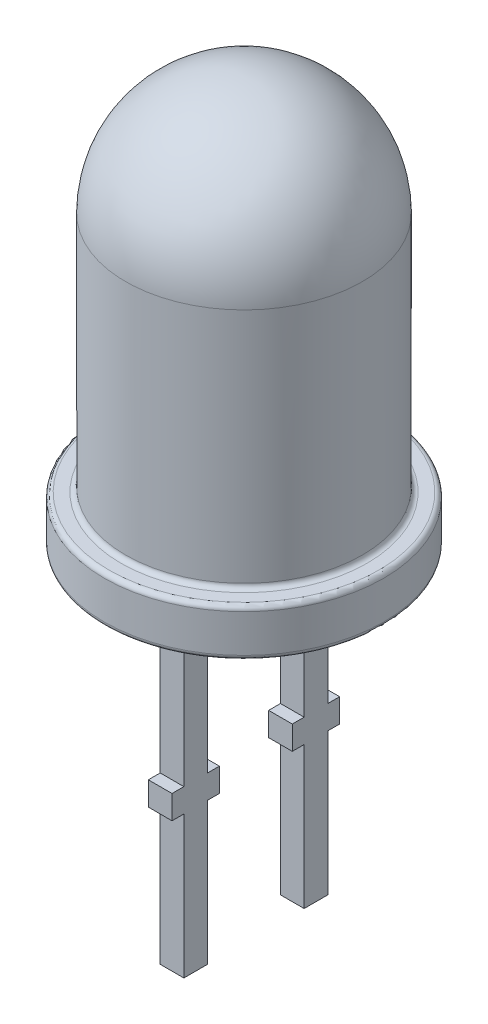
SolidWorks part; units mm, degrees
ref_plane "Спереди" through (0, 0, 0) normal (0, 0, 1) x (1, 0, 0)
ref_plane "Сверху" through (0, 0, 0) normal (0, 1, 0) x (1, 0, 0)
ref_plane "Справа" through (0, 0, 0) normal (1, 0, 0) x (0, 0, -1)
sketch "Эскиз1" plane through (0, 0, 0) normal (1, 0, 0) x (0, 0, -1)
  line L0 (4.8309, 0) -> (-4.1566, 0) construction
  line L1 (4.8309, 4) -> (-4.1566, 4) construction
  line L2 (0, -8.9757) -> (0, 8.1567) construction
  line L3 (-1.27, 7.7097) -> (-1.27, -11.3357) construction
  line L4 (-1.52, 4) -> (-1.52, 0.5)
  line L5 (-1.52, 0.5) -> (-1.77, 0.5)
  line L6 (-1.77, 0.5) -> (-1.77, 0)
  line L7 (-1.77, 0) -> (-1.52, 0)
  line L8 (-1.52, 0) -> (-1.52, -3)
  line L9 (-1.52, -3) -> (-1.02, -3)
  line L10 (-1.02, 0.5) -> (-1.02, 0) construction
  line L11 (-1.52, 0.5) -> (-1.52, 0) construction
  line L12 (-1.02, 0) -> (-1.02, -3)
  line L13 (-0.77, 0) -> (-1.02, 0)
  line L14 (-0.77, 0.5) -> (-0.77, 0)
  line L15 (-1.02, 0.5) -> (-0.77, 0.5)
  line L16 (-1.02, 4) -> (-1.02, 0.5)
  line L17 (1.52, 0.5) -> (1.52, 0) construction
  line L18 (1.02, 0.5) -> (1.02, 0) construction
  line L19 (1.02, 4) -> (1.02, 0.5)
  line L20 (1.02, 0.5) -> (0.77, 0.5)
  line L21 (0.77, 0.5) -> (0.77, 0)
  line L22 (0.77, 0) -> (1.02, 0)
  line L23 (1.02, 0) -> (1.02, -3)
  line L24 (1.52, -3) -> (1.02, -3)
  line L25 (1.52, 0) -> (1.52, -3)
  line L26 (1.77, 0) -> (1.52, 0)
  line L27 (1.77, 0.5) -> (1.77, 0)
  line L28 (1.52, 0.5) -> (1.77, 0.5)
  line L29 (1.52, 4) -> (1.52, 0.5)
  line L30 (-3.3588, 8) -> (3.258, 8) construction
  line L31 (1.52, 4) -> (1.52, 4.1)
  line L32 (1.62, 4.2) -> (1.72, 4.2)
  line L33 (1.82, 4.3) -> (1.82, 5.1764)
  line L34 (1.8094, 5.2211) -> (1.3647, 6.1106)
  line L35 (1.4094, 6.2447) -> (1.7549, 6.4174)
  line L36 (1.8101, 6.5069) -> (1.8101, 8)
  line L37 (1.8101, 8) -> (-0.7899, 8)
  line L38 (-0.7899, 8) -> (-0.7899, 7.4009)
  line L39 (-0.7423, 7.3158) -> (0.6225, 6.4744)
  line L40 (0.67, 6.3892) -> (0.67, 5.1594)
  line L41 (0.7221, 5.0716) -> (1.1027, 4.864)
  line L42 (1.1255, 4.7055) -> (1.0493, 4.6293)
  line L43 (1.02, 4.5586) -> (1.02, 4)
  line L44 (-1.02, 4) -> (-1.02, 4.5)
  line L45 (-0.92, 4.6) -> (-0.27, 4.6)
  line L46 (-0.17, 4.7) -> (-0.17, 5.9)
  line L47 (-0.07, 6) -> (0.03, 6)
  line L48 (0.13, 6.1) -> (0.13, 6.2408)
  line L49 (0.0825, 6.3259) -> (-1.0365, 7.0158)
  line L50 (-1.0841, 7.1009) -> (-1.0841, 8.1)
  line L51 (-1.0841, 8.1) -> (-1.7066, 8.1)
  line L52 (-1.7066, 8.1) -> (-1.7066, 6.8009)
  line L53 (-1.6591, 6.7158) -> (-1.2675, 6.4744)
  line L54 (-1.22, 6.3892) -> (-1.22, 6.05)
  line L55 (-1.26, 5.97) -> (-1.78, 5.58)
  line L56 (-1.82, 5.5) -> (-1.82, 4.3)
  line L57 (-1.72, 4.2) -> (-1.62, 4.2)
  line L58 (-1.52, 4.1) -> (-1.52, 4)
  line L59 (1.52, 4.2) -> (-2.5199, 4.2) construction
  line L60 (-0.17, 4.6) -> (2.6617, 4.6) construction
  line L61 (1.8101, 6.4451) -> (-2.4556, 6.4451) construction
  line L62 (0.13, 6) -> (-2.5199, 6) construction
  arc A0 (1.82, 4.3) -> (1.72, 4.2) centre (1.72, 4.3) cw
  arc A1 (1.52, 4.1) -> (1.62, 4.2) centre (1.62, 4.1) cw
  arc A2 (-0.7899, 7.4009) -> (-0.7423, 7.3158) centre (-0.6899, 7.4009) ccw
  arc A3 (0.6225, 6.4744) -> (0.67, 6.3892) centre (0.57, 6.3892) cw
  arc A4 (0.67, 5.1594) -> (0.7221, 5.0716) centre (0.77, 5.1594) ccw
  arc A5 (1.8101, 6.5069) -> (1.7549, 6.4174) centre (1.7101, 6.5069) cw
  arc A6 (1.4094, 6.2447) -> (1.3647, 6.1106) centre (1.4542, 6.1553) ccw
  arc A7 (1.8094, 5.2211) -> (1.82, 5.1764) centre (1.72, 5.1764) cw
  arc A8 (1.02, 4.5586) -> (1.0493, 4.6293) centre (1.12, 4.5586) cw
  arc A9 (1.1027, 4.864) -> (1.1255, 4.7055) centre (1.0548, 4.7762) cw
  arc A10 (-1.0841, 7.1009) -> (-1.0365, 7.0158) centre (-0.9841, 7.1009) ccw
  arc A11 (-1.7066, 6.8009) -> (-1.6591, 6.7158) centre (-1.6066, 6.8009) ccw
  arc A12 (-1.2675, 6.4744) -> (-1.22, 6.3892) centre (-1.32, 6.3892) cw
  arc A13 (-1.22, 6.05) -> (-1.26, 5.97) centre (-1.32, 6.05) cw
  arc A14 (-1.78, 5.58) -> (-1.82, 5.5) centre (-1.72, 5.5) ccw
  arc A15 (-1.82, 4.3) -> (-1.72, 4.2) centre (-1.72, 4.3) ccw
  arc A16 (-1.62, 4.2) -> (-1.52, 4.1) centre (-1.62, 4.1) cw
  arc A17 (-1.02, 4.5) -> (-0.92, 4.6) centre (-0.92, 4.5) cw
  arc A18 (-0.27, 4.6) -> (-0.17, 4.7) centre (-0.27, 4.7) ccw
  arc A19 (-0.17, 5.9) -> (-0.07, 6) centre (-0.07, 5.9) cw
  arc A20 (0.0825, 6.3259) -> (0.13, 6.2408) centre (0.03, 6.2408) cw
  arc A21 (0.13, 6.1) -> (0.03, 6) centre (0.03, 6.1) cw
  point P19 (-1.27, -3)
  point P34 (1.27, -3)
  point P69 (1.82, 4.2)
  point P75 (-0.7899, 7.3451)
  point P78 (0.67, 6.4451)
  point P81 (0.67, 5.1)
  point P87 (1.32, 6.2)
  point P90 (1.82, 5.2)
  point P93 (1.02, 4.6)
  point P96 (1.22, 4.8)
  point P99 (-1.0841, 7.0451)
  point P102 (-1.7066, 6.7451)
  point P105 (-1.22, 6.4451)
  point P108 (-1.22, 6)
  point P111 (-1.82, 5.55)
  point P114 (-1.82, 4.2)
  point P119 (-1.02, 4.6)
  point P125 (-0.17, 6)
  point P128 (0.13, 6.2966)
  dimension "D30" = 0.1
  dimension "D1" = 4
  dimension "D2" = 1.27
  dimension "D3" = 0.5
  dimension "D4" = 1
  dimension "D5" = 0.5
  dimension "D6" = 3
  dimension "D7" = 0.3
  dimension "D8" = 0.2
  dimension "D9" = 0.4
  dimension "D10" = 1
  dimension "D11" = 0.5
  dimension "D12" = 0.2
  dimension "D13" = 4
  dimension "D14" = 2
  dimension "D15" = 2.2451
  dimension "D16" = 0.5
  dimension "D17" = 0.2
  dimension "D18" = 0.35
  dimension "D19" = 2.6
  dimension "D20" = 0.9
  dimension "D21" = 0.85
  dimension "D22" = 0.3
  dimension "D23" = 0.2966
  dimension "D24" = 1.8
  dimension "D25" = 1.35
  dimension "D26" = 0.6
  dimension "D27" = 0.3
  dimension "D28" = 0.6
  dimension "D29" = 0.1
extrude "Бобышка-Вытянуть1" add sketch "Эскиз1" along normal blind 0.25 and the other way blind 0.25
sketch "Эскиз2" plane through (0, 0, 0) normal (1, 0, 0) x (0, 0, -1)
  line L0 (0, 0) -> (0, 9.0521) construction
  line L1 (0, 8.0012) -> (-0.6, 8.0012)
  line L2 (-0.6, 8.0012) -> (-0.6, 7.8012)
  line L3 (-0.6, 7.8012) -> (0, 7.0012)
  line L4 (0, 7.0012) -> (0, 8.0012)
  dimension "D1" = 1.2
  dimension "D2" = 0.2
  dimension "D3" = 1
  dimension "D4" = 8.0012
revolve "Повернуть2" add sketch "Эскиз2" angle 360 about L0
sketch "Эскиз3" plane through (0, 0, 0) normal (1, 0, 0) x (0, 0, -1)
  line L0 (0, 8.0047) -> (0.55, 8.0047)
  line L1 (0.55, 8.0047) -> (0.55, 7.9947)
  line L2 (0.55, 7.9947) -> (0.15, 7.9047)
  line L3 (0.15, 7.9047) -> (0, 7.9047)
  line L4 (0, -8.9757) -> (0, 8.1567) construction
  line L5 (0, 7.9047) -> (0, 8.0047)
  dimension "D1" = 8.0047
  dimension "D2" = 0.15
  dimension "D3" = 0.01
  dimension "D4" = 0.1
  dimension "D5" = 0.55
revolve "Вырез-Повернуть1" cut sketch "Эскиз3" angle 360 about L2
sketch "Эскиз4" plane through (0, 7.9047, 0) normal (0, 1, 0) x (1, 0, 0)
  line L1 (-0.1, -0.1) -> (0.1, -0.1)
  line L2 (-0.1, -0.1) -> (-0.1, 0.1)
  line L3 (-0.1, 0.1) -> (0.1, 0.1)
  line L4 (0.1, -0.1) -> (0.1, 0.1)
  line L5 (-0.1, -0.1) -> (0.1, 0.1) construction
  line L6 (-0.1, 0.1) -> (0.1, -0.1) construction
  point P0 (0, 0)
  dimension "D1" = 0.2
  dimension "D2" = 0.2
extrude "Бобышка-Вытянуть2" add sketch "Эскиз4" along normal blind 0.05
sketch "Эскиз6" plane through (0, 7.9547, 0) normal (0, 1, 0) x (1, 0, 0)
  circle A0 centre (0, 0) radius 0.02
  dimension "D1" = 0.04
sketch3d "Трехмерный эскиз2"
  line L0 (0, 7.9547, 0) -> (0, 7.9673, 0)
  line L1 (0, -8.9757, 0) -> (0, 8.1567, 0) construction
  line L2 (-0.25, 8.1, 1.7066) -> (0.25, 8.1, 1.0841) construction
  line L3 (-0.25, 8.1, 1.0841) -> (0.25, 8.1, 1.7066) construction
  line L4 (0, 8.1, 1.3953) -> (0, 8.1042, 1.3953)
  line L5 (0, 8.154, 1.3497) -> (0, 8.1964, 0.8702)
  line L6 (0, 8.163, 0.536) -> (0, 8.0153, 0.0358)
  arc A0 (0, 7.9673, 0) -> (0, 8.0153, 0.0358) centre (0, 7.9673, 0.05) ccw
  arc A1 (0, 8.1042, 1.3953) -> (0, 8.154, 1.3497) centre (0, 8.1042, 1.3453) ccw
  arc A2 (0, 8.163, 0.536) -> (0, 8.1964, 0.8702) centre (0, 7.2999, 0.7909) ccw
  point P18 (0, 8.0047, 0)
  point P19 (0.05, 7.9673, 0.05)
  point P22 (0, 8.15, 1.3953)
  point P23 (-0.05, 8.1042, 1.3453)
  point P26 (0, 8.2115, 0.6999)
  point P27 (0.9, 7.2999, 0.7909)
  dimension "D3" = 0.05
  dimension "D4" = 0.9
  dimension "D1" = 0.05
  dimension "D2" = 0.05
sweep "По траектории1" add profiles "Эскиз6" path "Трехмерный эскиз2"
sketch "Эскиз7" plane through (0, 0, 0) normal (1, 0, 0) x (0, 0, -1)
  line L0 (0, 4) -> (2.95, 4)
  line L1 (4.8309, 4) -> (-4.1566, 4) construction
  line L2 (0, -8.9757) -> (0, 8.1567) construction
  line L3 (2.95, 4) -> (2.95, 5)
  line L4 (2.95, 5) -> (2.5, 5)
  line L5 (2.5, 5) -> (2.5, 10.1)
  line L6 (0, 0) -> (0, 13.3429) construction
  line L7 (0, 12.6) -> (0, 12.5025)
  line L8 (0, 4.1) -> (2.85, 4.1)
  line L9 (2.85, 4.1) -> (2.85, 4.9)
  line L10 (2.85, 4.9) -> (2.4025, 4.9)
  line L11 (2.4025, 4.9) -> (2.4025, 10.1)
  line L12 (0, 4.1) -> (0, 4)
  line L13 (0, 10.1) -> (4.3229, 10.1) construction
  arc A0 (2.5, 10.1) -> (0, 12.6) centre (0, 10.1) ccw
  arc A1 (2.4025, 10.1) -> (0, 12.5025) centre (0, 10.1) ccw
  dimension "D1" = 2.5
  dimension "D2" = 8.6
  dimension "D3" = 1
  dimension "D4" = 5
  dimension "D5" = 5.9
  dimension "D6" = 0.1
  dimension "D7" = 0.1
  dimension "D8" = 0.1
  dimension "D9" = 0.0975
  dimension "D10" = 0.0975
revolve "Повернуть3" add sketch "Эскиз7" angle 360 about L6
fillet "Скругление1" radius 0.1 3 edges at (0, 5, -2.5) (0, 4, -2.95) (0, 5, -2.95)
fillet "Скругление2" radius 0.1 8 edges at (0, 4, 1.02) (0, 4, 1.52) (0.25, 4, 1.27) (-0.25, 4, 1.27) (0, 4, -1.52) (-0.25, 4, -1.27) (0, 4, -1.02) (0.25, 4, -1.27)
equation "\"D10@Эскиз7\"=\"D1@Эскиз7\"-0.1"
